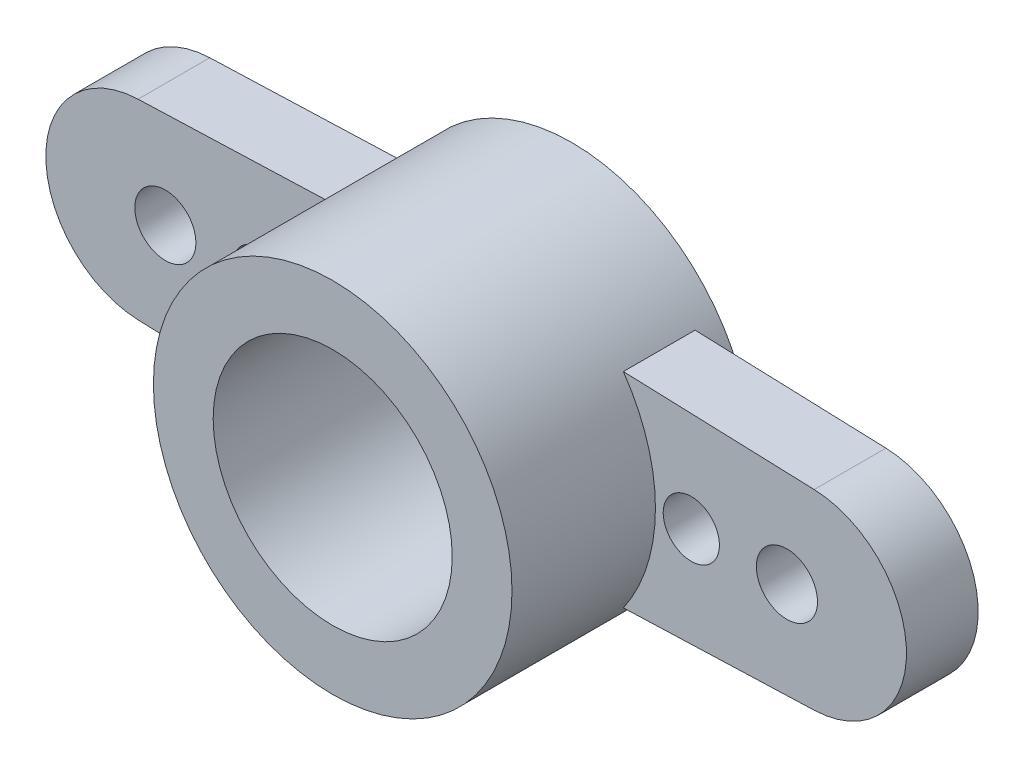
SolidWorks part; units mm, degrees
ref_plane "Спереди" through (0, 0, 0) normal (0, 0, 1) x (1, 0, 0)
ref_plane "Сверху" through (0, 0, 0) normal (0, 1, 0) x (1, 0, 0)
ref_plane "Справа" through (0, 0, 0) normal (1, 0, 0) x (0, 0, -1)
sketch "Эскиз1" plane through (0, 0, 0) normal (0, 0, 1) x (1, 0, 0)
  line L0 (0, 0) -> (-7, 0)
  line L1 (-7.0708, 1.9987) -> (0, 2.2493)
  line L2 (-7.0708, -1.9987) -> (0, -2.2493)
  line L4 (14.0708, -1.7507) -> (0, -2.2493)
  line L5 (14.0708, 1.7507) -> (0, 2.2493)
  circle A0 centre (0, 0) radius 3.75
  circle A1 centre (0, 0) radius 2.5
  arc A2 (-6.967, -1.9997) -> (-7.0708, 1.9987) centre (-7, 0) cw
  arc A3 (13.967, -2.2478) -> (14.0708, 1.7507) centre (14, -0.2481) ccw
  dimension "D1" = 7.5
  dimension "D2" = 5
  dimension "D4" = 2
  dimension "D3" = 7
extrude "Бобышка-Вытянуть3" add sketch "Эскиз1" along normal blind 1.5 contours L4 A3 L5 A0 | A2 L2 A0 L1 region at (-3.6481, -1.1433, 0) region at (2.794, 0, 0)
sketch "Эскиз2" plane through (0, 0, 1.5) normal (0, 0, 1) x (1, 0, 0)
  circle A0 centre (0, 0) radius 3.75
  circle A1 centre (0, 0) radius 2.5
  dimension "D1" = 5
extrude "Бобышка-Вытянуть5" add sketch "Эскиз2" along normal blind 3 separate body
sketch "Эскиз3" plane through (0, 0, 1.5) normal (0, 0, -1) x (-1, 0, 0)
  circle A0 centre (0, 0) radius 3.75
  circle A1 centre (0, 0) radius 2.5
extrude "Бобышка-Вытянуть6" add sketch "Эскиз3" along normal blind 2
sketch "Esquisse1" plane through (0, 0, 1.5) normal (0, 0, 1) x (1, 0, 0)
  circle A0 centre (-4.5, 0) radius 0.5879
  circle A1 centre (-6.5, 0) radius 0.639
  dimension "D1" = 4.5
  dimension "D2" = 2
extrude "Enlèv. mat.-Extru.1" cut sketch "Esquisse1" against normal blind 10
pattern_circular "Répétition circulaire1" count 2 over 360 about axis through (0, 0, 4.5) along (0, 0, 1) of "Enlèv. mat.-Extru.1", "Бобышка-Вытянуть3"
